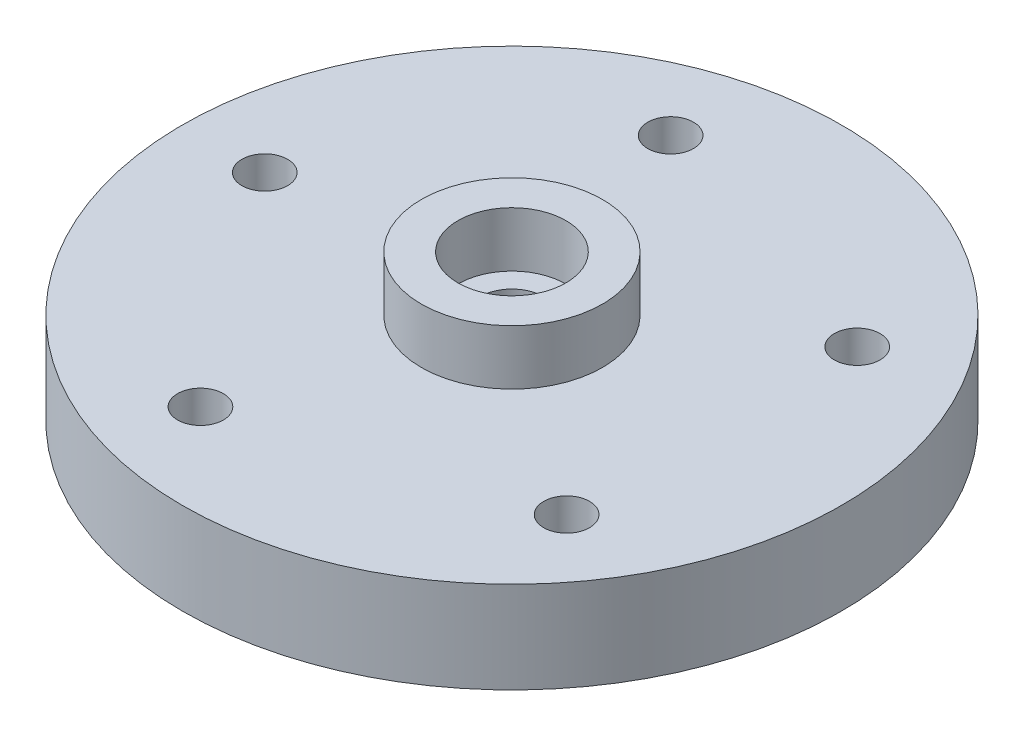
SolidWorks part; units mm, degrees
ref_plane "Front Plane" through (0, 0, 0) normal (0, 0, 1) x (1, 0, 0)
ref_plane "Top Plane" through (0, 0, 0) normal (0, 1, 0) x (1, 0, 0)
ref_plane "Right Plane" through (0, 0, 0) normal (1, 0, 0) x (0, 0, -1)
sketch "Sketch1" plane through (0, 0, 0) normal (0, 1, 0) x (1, 0, 0)
  line L0 (-13.5, 0) -> (13.5, 0) construction
  circle A0 centre (0, 0) radius 16
  circle A1 centre (0, 0) radius 13.5
  circle A2 centre (0, 0) radius 1.75
  circle A3 centre (-13.5, 0) radius 1.25
  circle A4 centre (-4.1717, 12.8393) radius 1.25
  circle A5 centre (10.9217, 7.9351) radius 1.25
  circle A6 centre (10.9217, -7.9351) radius 1.25
  circle A7 centre (-4.1717, -12.8393) radius 1.25
  point P19 (0, 0)
  dimension "D1" = 32
  dimension "D2" = 2.5
  dimension "D3" = 3.5
  dimension "D4" = 2.5
  dimension "D5" = 5
extrude "Boss-Extrude1" add sketch "Sketch1" along normal blind 2 and the other way blind 3 contours A0 A7 A1 A3 A4 A5 A6 | L0 A3 A1 A7 A6 A2 | A3 L0 A2 A1 A5 A4 region at (0, 0, -5.7653) region at (0, 0, 5.7653) region at (-15.5475, 0, 0)
sketch "Sketch2" plane through (0, 2, 0) normal (0, 1, 0) x (1, 0, 0)
  circle A0 centre (0, 0) radius 2.95
  circle A1 centre (0, 0) radius 4.95
  dimension "D1" = 5.9
  dimension "D2" = 2
extrude "Boss-Extrude3" add sketch "Sketch2" along normal blind 3 contours A1 A0 region at (-4.81, 2, 0)
sketch "Sketch4" plane through (0, 2, 0) normal (0, 1, 0) x (1, 0, 0)
  circle A0 centre (0, 0) radius 2
sketch "Sketch5" plane through (0, -3, 0) normal (0, -1, 0) x (1, 0, 0)
  circle A0 centre (0, 0) radius 3.5
  dimension "D1" = 7
extrude "Cut-Extrude2" cut sketch "Sketch5" against normal blind 4
sketch "Sketch6" plane through (0, 2, 0) normal (0, 1, 0) x (1, 0, 0)
  circle A0 centre (0, 0) radius 16
  circle A1 centre (0, 0) radius 18
  dimension "D1" = 2
extrude "Boss-Extrude4" add sketch "Sketch6" against normal blind 5
